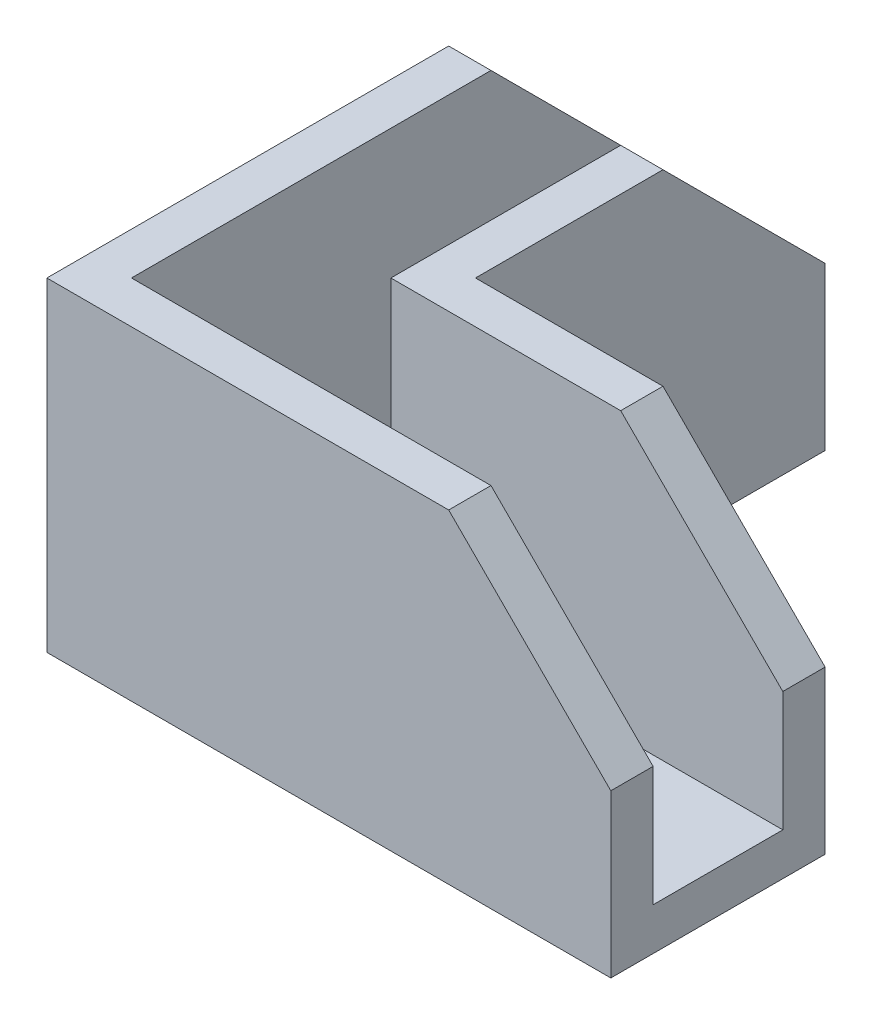
SolidWorks part; units mm, degrees
ref_plane "前视基准面" through (0, 0, 0) normal (0, 0, 1) x (1, 0, 0)
ref_plane "上视基准面" through (0, 0, 0) normal (0, 1, 0) x (1, 0, 0)
ref_plane "右视基准面" through (0, 0, 0) normal (1, 0, 0) x (0, 0, -1)
other "Configuration Table"
sketch "草图1" plane through (0, 0, 0) normal (0, 1, 0) x (1, 0, 0)
  line L5 (15.2, 15.2) -> (40, 15.2)
  line L7 (0, 40) -> (15.2, 40)
  line L8 (0, 40) -> (0, 0)
  line L9 (0, 0) -> (40, 0)
  line L10 (15.2, 40) -> (15.2, 15.2)
  line L12 (40, 15.2) -> (40, 0)
  line L13 (3, 40) -> (12.2, 40)
  line L14 (3, 40) -> (3, 3)
  line L16 (12.2, 40) -> (12.2, 12.2)
  line L17 (12.2, 12.2) -> (40, 12.2)
  line L19 (3, 3) -> (40, 3)
  line L20 (40, 12.2) -> (40, 3)
  point P13 (0, 0)
  dimension "D1" = 40
  dimension "D2" = 40
  dimension "D3" = 3
  dimension "D4" = 3
  dimension "D5" = 9.2
  dimension "D6" = 3
  dimension "D7" = 9.2
  dimension "D8" = 3
extrude "凸台-拉伸1" add sketch "草图1" against normal blind 3 contours L16 L17 L12 L5 L10 L7 | L14 L19 L12 L17 L16 L7 | L19 L14 L7 L8 L9 L12 region at (27.6, 0, -14.8068) region at (39.4767, 0, -7.6) region at (39.4343, 0, -1.5)
extrude "凸台-拉伸2" add sketch "草图1<3>" along normal blind 20 contours L19 L14 L7 L8 L9 L12 | L16 L17 L12 L5 L10 L7 region at (27.6, 0, -14.8068) region at (39.4343, 0, -1.5)
sketch "草图1<3>" plane through (0, 0, 0) normal (0, 1, 0) x (1, 0, 0) same geometry as "草图1"
sketch "草图2" plane through (0, 0, 0) normal (-1, 0, 0) x (0, 0, 1)
  line L5 (-40, 8.5) -> (-28.5, 20)
  line L6 (-40, -3) -> (-40, 20) construction
  line L7 (-40, 20) -> (0, 20) construction
  line L8 (-40, 8.5) -> (-40, 20)
  line L9 (-40, 20) -> (-28.5, 20)
  dimension "D1" = 45
extrude "切除-拉伸1" cut sketch "草图2" against normal through all
sketch "草图3" plane through (0, 0, -15.2) normal (0, 0, -1) x (-1, 0, 0)
  line L0 (-40, 8.5) -> (-28.5, 20)
  line L1 (-40, -3) -> (-40, 20) construction
  line L2 (-15.2, 20) -> (-40, 20) construction
  line L3 (-28.5, 20) -> (-40, 20)
  line L4 (-40, 20) -> (-40, 8.5)
  dimension "D1" = 45
extrude "切除-拉伸2" cut sketch "草图3" against normal through all
